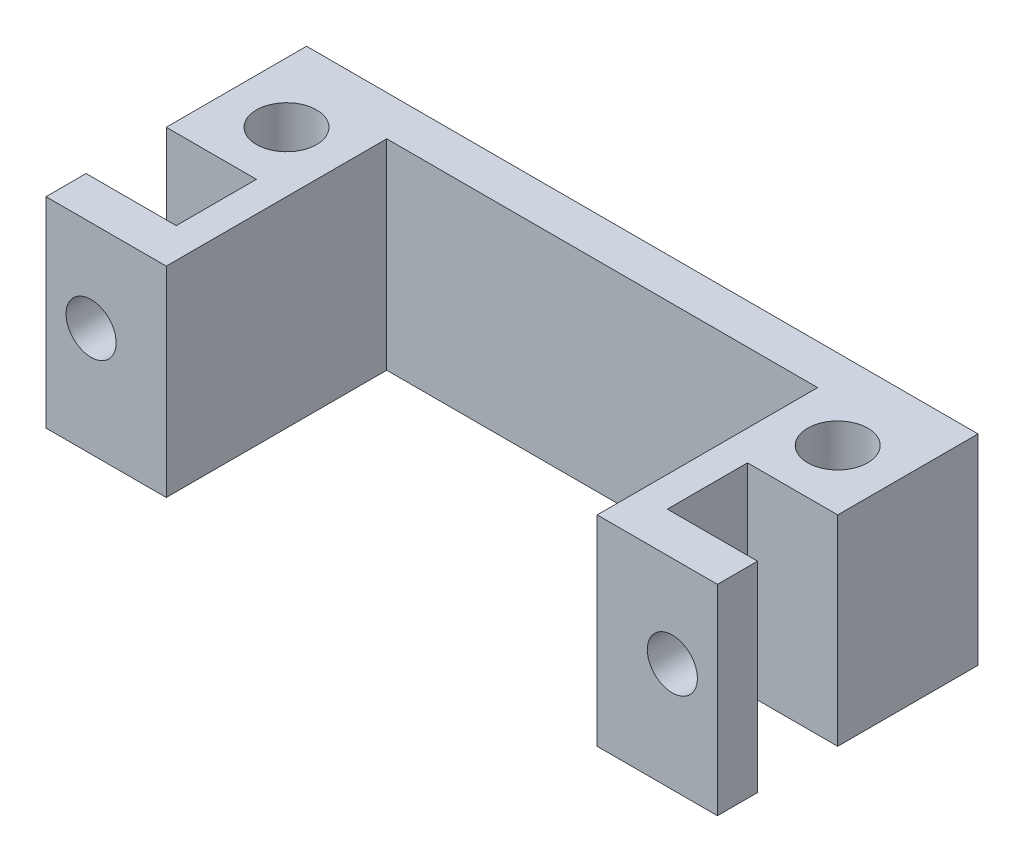
SolidWorks part; units mm, degrees
ref_plane "Front Plane" through (0, 0, 0) normal (0, 0, 1) x (1, 0, 0)
ref_plane "Top Plane" through (0, 0, 0) normal (0, 1, 0) x (1, 0, 0)
ref_plane "Right Plane" through (0, 0, 0) normal (1, 0, 0) x (0, 0, -1)
sketch "Sketch1" plane through (0, 0, 0) normal (0, 1, 0) x (1, 0, 0)
  line L0 (69.85, 0) -> (85.09, 0)
  line L1 (0, 0) -> (15.24, 0)
  line L2 (0, 0) -> (0, 5.08)
  line L3 (0, 33.02) -> (85.09, 33.02)
  line L4 (85.09, 0) -> (85.09, 5.08)
  line L6 (15.24, 0) -> (15.24, 27.94)
  line L7 (15.24, 27.94) -> (69.85, 27.94)
  line L8 (69.85, 0) -> (69.85, 27.94)
  line L9 (0, 15.24) -> (11.43, 15.24)
  line L10 (11.43, 15.24) -> (11.43, 5.08)
  line L11 (11.43, 5.08) -> (0, 5.08)
  line L12 (85.09, 15.24) -> (73.66, 15.24)
  line L13 (73.66, 15.24) -> (73.66, 5.08)
  line L14 (73.66, 5.08) -> (85.09, 5.08)
  line L15 (0, 15.24) -> (0, 33.02)
  line L16 (85.09, 15.24) -> (85.09, 33.02)
  point P15 (9.187, 15.24)
  dimension "D1" = 15.24
  dimension "D2" = 15.24
  dimension "D3" = 27.94
  dimension "D4" = 54.61
  dimension "D5" = 5.08
  dimension "D6" = 5.08
  dimension "D7" = 10.16
  dimension "D8" = 3.81
extrude "Boss-Extrude1" add sketch "Sketch1" along normal blind 25.4
sketch "Sketch2" plane through (0, 25.4, 0) normal (0, 1, 0) x (1, 0, 0)
  line L0 (0, 0) -> (15.24, 0) construction
  line L1 (69.85, 0) -> (85.09, 0) construction
  line L2 (85.09, 33.02) -> (0, 33.02) construction
  circle A0 centre (7.62, 22.86) radius 3.81
  circle A1 centre (77.47, 22.86) radius 3.81
  point P6 (7.62, 0)
  point P9 (77.47, 0)
  point P10 (0, 0)
  dimension "D1" = 7.62
  dimension "D2" = 10.16
extrude "Cut-Extrude1" cut sketch "Sketch2" against normal through all
hole_wizard "1/4 (0.25) Diameter Hole1" positions "Sketch3" profile "Sketch4" hole size "1/4" standard "ANSI Inch"
sketch "Sketch3" plane through (0, 0, 0) normal (0, 0, 1) x (1, 0, 0)
  line L0 (5.715, 13.8028) -> (79.375, 13.8028) construction
  line L4 (15.24, 0) -> (69.85, 0) construction
  line L5 (42.545, 13.8028) -> (42.545, 0) construction
  point P0 (5.715, 13.8028)
  point P2 (79.375, 13.8028)
  dimension "D1" = 73.66
sketch "Sketch4" plane through (5.715, 13.8028, 0) normal (1, 0, 0) x (0, -1, 0)
  line L0 (0, 0) -> (0, 9.5277)
  line L1 (0, 9.5277) -> (3.175, 7.62)
  line L2 (3.175, 7.62) -> (3.175, 0)
  line L5 (3.175, 0) -> (0, 0)
  line L10 (0, 9.5277) -> (-3.175, 7.62) construction
  line L11 (0, -6.35) -> (0, 107.95) construction
  dimension "Hole Dia." = 6.35
  dimension "Hole Depth" = 7.62
  dimension "Drill Angle" = 118
hole_wizard "1/4 (0.25) Diameter Hole2" positions "Sketch5" profile "Sketch6" hole size "1/4" standard "ANSI Inch"
sketch "Sketch5" plane through (0, 0, -33.02) normal (0, 0, -1) x (-1, 0, 0)
  line L2 (-85.09, 0) -> (0, 0) construction
  line L3 (-42.545, 0) -> (-42.545, 12.7) construction
  line L11 (-77.47, 12.7) -> (-7.62, 12.7) construction
  point P0 (-77.47, 12.7)
  point P2 (-7.62, 12.7)
  point P42 (-42.545, 12.7)
  dimension "D1" = 69.85
sketch "Sketch6" plane through (77.47, 12.7, -33.02) normal (1, 0, 0) x (0, 1, 0)
  line L0 (0, 0) -> (0, 12.0677)
  line L1 (0, 12.0677) -> (3.175, 10.16)
  line L2 (3.175, 10.16) -> (3.175, 0)
  line L5 (3.175, 0) -> (0, 0)
  line L10 (0, 12.0677) -> (-3.175, 10.16) construction
  line L11 (0, -6.35) -> (0, 107.95) construction
  dimension "Hole Dia." = 6.35
  dimension "Hole Depth" = 10.16
  dimension "Drill Angle" = 118
equation "\"D2@Sketch1\"=\"D1@Sketch1\""
